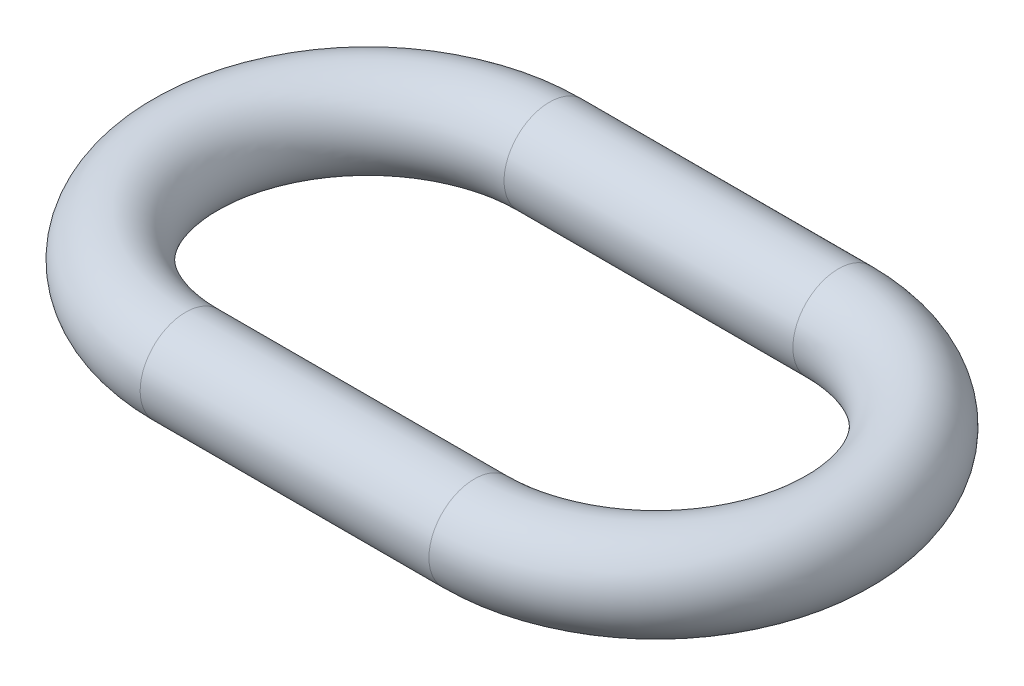
SolidWorks part; units mm, degrees
ref_plane "Front Plane" through (0, 0, 0) normal (0, 0, 1) x (1, 0, 0)
ref_plane "Top Plane" through (0, 0, 0) normal (0, 1, 0) x (1, 0, 0)
ref_plane "Right Plane" through (0, 0, 0) normal (1, 0, 0) x (0, 0, -1)
sketch "Sketch1" plane through (0, 0, 0) normal (0, 1, 0) x (1, 0, 0)
  line L0 (0, 7.5883) -> (0, -7.9238) construction
  line L1 (0, -7.9238) -> (0, -9.3255) construction
  line L2 (14.6686, 0) -> (-14.113, 0) construction
  line L3 (-4.0312, 5.08) -> (4.0312, 5.08)
  line L4 (-4.0312, -5.08) -> (4.0312, -5.08)
  arc A1 (4.0312, 5.08) -> (4.0312, -5.08) centre (4.0312, 0) cw
  arc A2 (-4.0312, 5.08) -> (-4.0312, -5.08) centre (-4.0312, 0) ccw
  point P9 (0, 5.08)
  dimension "D1" = 5.08
sweep "Sweep1" add path "Sketch1" circular profile diameter 2.54 parameters "D3"=2.54
